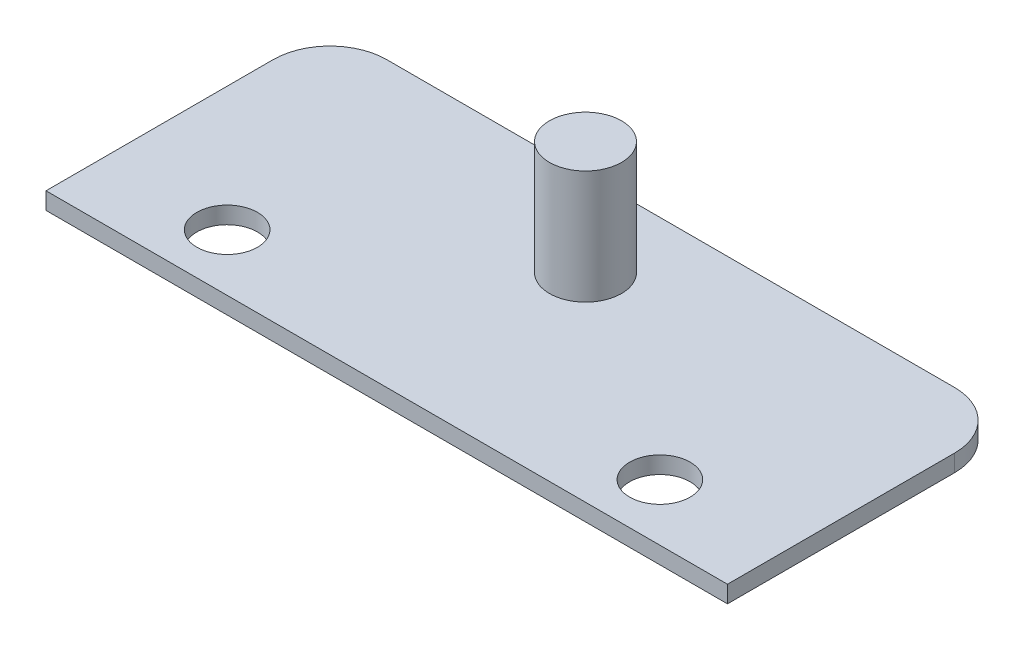
SolidWorks part; units mm, degrees
ref_plane "Front Plane" through (0, 0, 0) normal (0, 0, 1) x (1, 0, 0)
ref_plane "Top Plane" through (0, 0, 0) normal (0, 1, 0) x (1, 0, 0)
ref_plane "Right Plane" through (0, 0, 0) normal (1, 0, 0) x (0, 0, -1)
sketch "Sketch1" plane through (0, 0, 0) normal (0, 1, 0) x (1, 0, 0)
  line L1 (0, 0) -> (120, 0)
  line L2 (0, 0) -> (0, 50)
  line L3 (0, 50) -> (120, 50)
  line L4 (120, 0) -> (120, 50)
  dimension "D1" = 50
  dimension "D2" = 120
extrude "Boss-Extrude1" add sketch "Sketch1" along normal blind 3
sketch "Sketch2" plane through (0, 3, 0) normal (0, 1, 0) x (1, 0, 0)
  line L0 (60, 50) -> (60, 0) construction
  line L1 (120, 50) -> (0, 50) construction
  line L2 (0, 0) -> (120, 0) construction
  circle A0 centre (21.9, 10) radius 5.334
  circle A1 centre (98.1, 10) radius 5.334
  dimension "D1" = 10.668
  dimension "D2" = 76.2
  dimension "D3" = 10
extrude "Cut-Extrude1" cut sketch "Sketch2" against normal through all
sketch "Sketch3" plane through (0, 3, 0) normal (0, 1, 0) x (1, 0, 0)
  line L0 (60, 50) -> (60, 0) construction
  line L1 (120, 50) -> (0, 50) construction
  line L2 (0, 0) -> (120, 0) construction
  circle A0 centre (60, 35) radius 6.35
  dimension "D2" = 12.7
  dimension "D1" = 15
extrude "Boss-Extrude2" add sketch "Sketch3" along normal blind 20
fillet "Fillet1" radius 10 2 edges at (120, 1.5, -50) (0, 1.5, -50)
